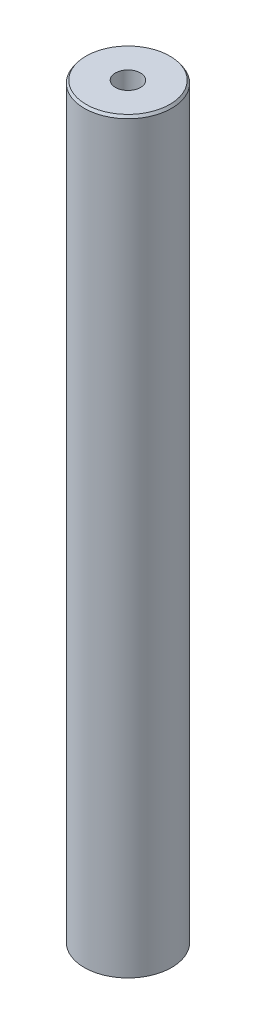
SolidWorks part; units mm, degrees
ref_plane "Front Plane" through (0, 0, 0) normal (0, 0, 1) x (1, 0, 0)
ref_plane "Top Plane" through (0, 0, 0) normal (0, 1, 0) x (1, 0, 0)
ref_plane "Right Plane" through (0, 0, 0) normal (1, 0, 0) x (0, 0, -1)
sketch "Sketch1" plane through (0, 0, 0) normal (0, 1, 0) x (1, 0, 0)
  circle A0 centre (0, 0) radius 35
  dimension "SHAFT_OD" = 70
extrude "Boss-Extrude1" add sketch "Sketch1" along normal blind 600
sketch "Sketch2" plane through (0, 0, 0) normal (0, 1, 0) x (1, 0, 0)
  circle A0 centre (0, 0) radius 10.0819
  dimension "BORE_D" = 20.1639
extrude "Cut-Extrude1" cut sketch "Sketch2" along normal through all
chamfer "Chamfer1" distance 2.0324 angle 34.841 2 edges at (0, 600, 35) (0, 0, 35) first distance on face at (0, 600, 35) first distance on face at (0, 0, 10.0819)
